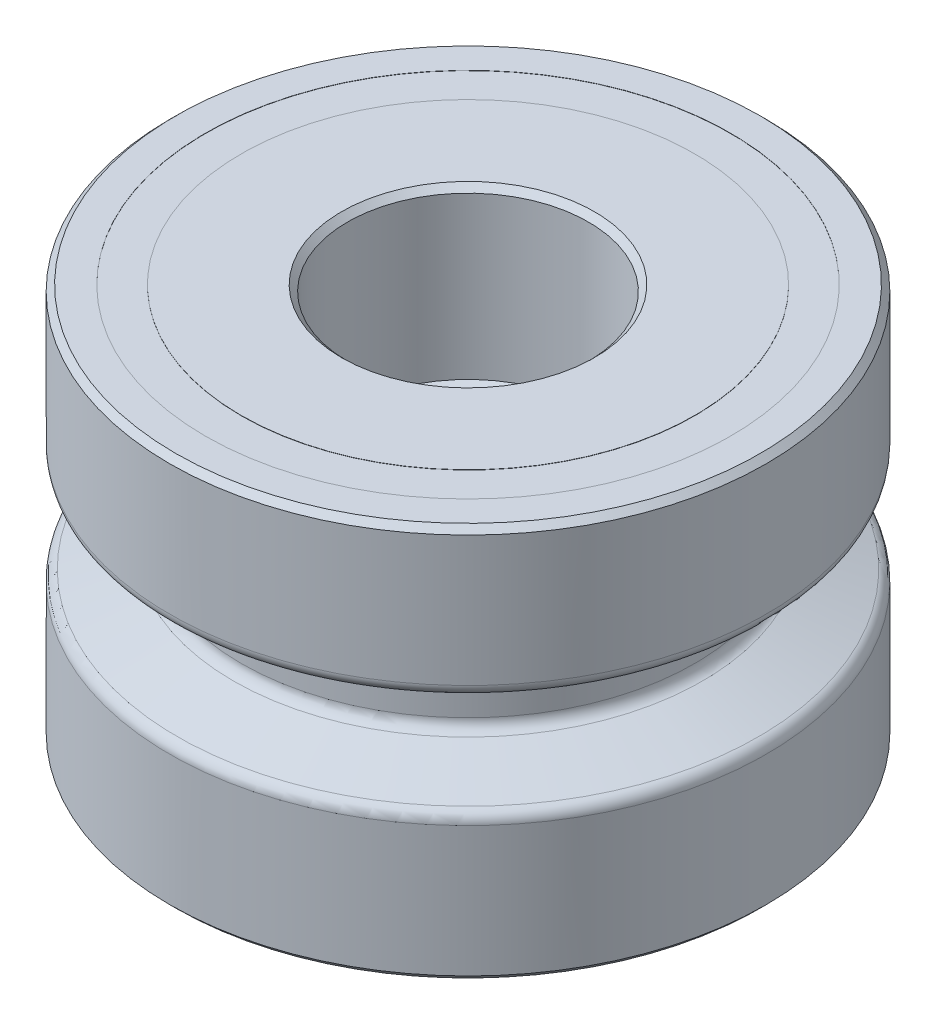
SolidWorks part; units mm, degrees
ref_plane "Front Plane" through (0, 0, 0) normal (0, 0, 1) x (1, 0, 0)
ref_plane "Top Plane" through (0, 0, 0) normal (0, 1, 0) x (1, 0, 0)
ref_plane "Right Plane" through (0, 0, 0) normal (1, 0, 0) x (0, 0, -1)
sketch "Sketch1" plane through (0, 0, 0) normal (0, 1, 0) x (1, 0, 0)
  circle A0 centre (0, 0) radius 12.5
  dimension "D1" = 25
extrude "Boss-Extrude1" add sketch "Sketch1" along normal mid plane 16.5
sketch "Sketch2" plane through (0, -8.25, 0) normal (0, -1, 0) x (1, 0, 0)
  circle A1 centre (0, 0) radius 4
  dimension "D1" = 8
extrude "Cut-Extrude1" cut sketch "Sketch2" against normal up to next
sketch "Sketch11" plane through (0, -8.25, 0) normal (0, -1, 0) x (1, 0, 0)
  circle A0 centre (0, 0) radius 5.05
  dimension "D1" = 10.1
extrude "Cut-Extrude5" cut sketch "Sketch11" against normal blind 4
sketch "Sketch12" plane through (0, 8.25, 0) normal (0, 1, 0) x (1, 0, 0)
  circle A0 centre (0, 0) radius 5.05 construction
  circle A1 centre (0, 0) radius 5.05
extrude "Cut-Extrude6" cut sketch "Sketch12" against normal blind 7
sketch "Sketch7" plane through (0, 8.25, 0) normal (0, 1, 0) x (1, 0, 0)
  circle A1 centre (0, 0) radius 9.5
  circle A2 centre (0, 0) radius 11
  circle A3 centre (0, 0) radius 11
  dimension "D1" = 1.5
  dimension "D2" = 1.5
extrude "Cut-Extrude4" cut sketch "Sketch7" against normal blind 0.01 contours A3 A1 region at (-10.6889, 8.25, 0)
ref_axis "Axis1" through (0, 8.25, 0) along (0, -1, 0)
sketch "Sketch10" plane through (0, 0, 0) normal (0, 0, 1) x (1, 0, 0)
  line L0 (-4.2808, 0) -> (5.2603, 0) construction
  line L1 (12.5, 2.1919) -> (9.5, 1.1)
  line L2 (12.5, -8.25) -> (12.5, 8.25) construction
  line L4 (12.5, -2.1919) -> (9.5, -1.1)
  line L5 (12.5, 2.1919) -> (12.5, -2.1919)
  line L6 (9.5, 1.1) -> (9.5, -1.1)
  line L7 (9.5, 1.1) -> (12.5, 1.1) construction
  dimension "D1" = 3
  dimension "D2" = 2.2
  dimension "D3" = 20
revolve "Cut-Revolve1" cut sketch "Sketch10" angle 360 about axis through (0, 8.25, 0) along (0, -1, 0)
chamfer "Chamfer2" distance 0.5 angle 65 1 edges at (0, 1.25, 4) first distance on face at (0, -4.25, -4)
fillet "Fillet4" radius 0.5 4 edges at (0, -1.1, 9.5) (0, 1.1, 9.5) (0, 2.1919, 12.5) (0, -2.1919, 12.5)
chamfer "Chamfer1" distance 0.25 angle 45 5 edges at (0, -8.25, 12.5) (0, 8.25, 12.5) (0, -8.25, -5.05) (0, 8.25, 5.05) (0, -4.25, -4)
